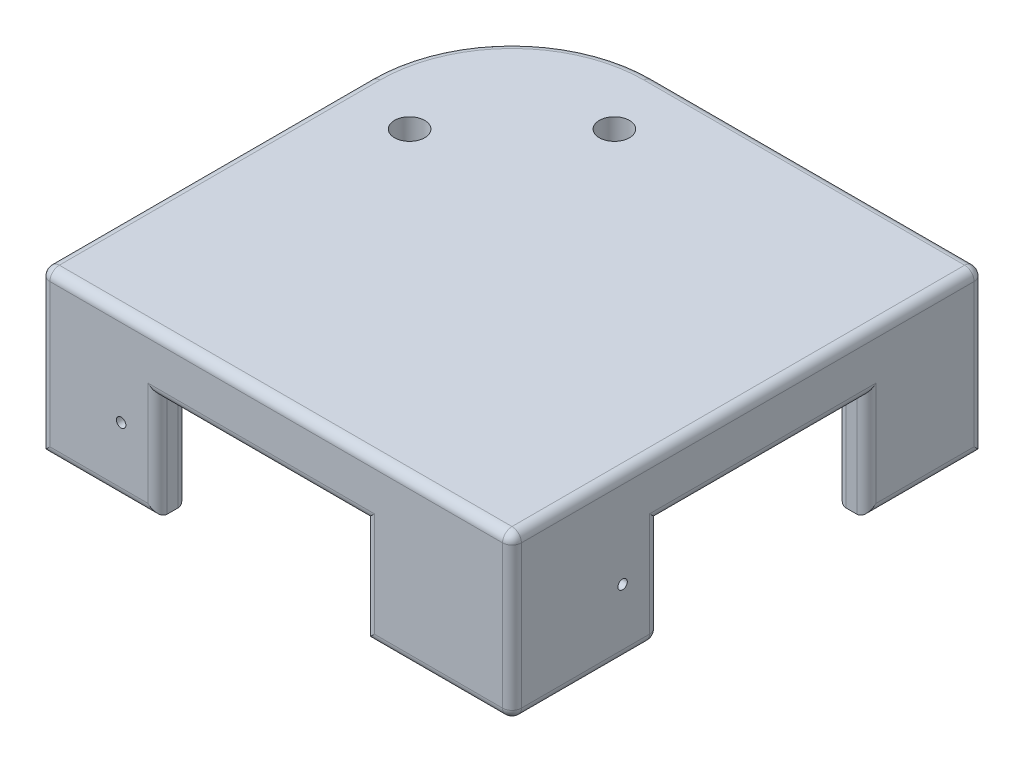
SolidWorks part; units mm, degrees
ref_plane "Front Plane" through (0, 0, 0) normal (0, 0, 1) x (1, 0, 0)
ref_plane "Top Plane" through (0, 0, 0) normal (0, 1, 0) x (1, 0, 0)
ref_plane "Right Plane" through (0, 0, 0) normal (1, 0, 0) x (0, 0, -1)
sketch "Sketch1" plane through (0, 0, 0) normal (0, 1, 0) x (1, 0, 0)
  line L1 (-25, 25) -> (25, 25)
  line L2 (-25, 25) -> (-25, -25)
  line L3 (-25, -25) -> (25, -25)
  line L4 (25, 25) -> (25, -25)
  line L5 (-25, 25) -> (25, -25) construction
  line L6 (-25, -25) -> (25, 25) construction
  point P0 (0, 0)
  dimension "D1" = 50
  dimension "D2" = 50
extrude "Boss-Extrude1" add sketch "Sketch1" along normal blind 3.175
sketch "Sketch2" plane through (0, 0, 0) normal (0, -1, 0) x (-1, 0, 0)
  line L0 (-25, -25) -> (-25, 25) construction
  line L1 (25, -25) -> (-25, -25)
  line L2 (25, -25) -> (25, -21.825)
  line L3 (25, -21.825) -> (-25, -21.825)
  line L4 (-25, -25) -> (-25, -21.825)
  line L5 (25, -25) -> (-25, -21.825) construction
  line L6 (25, -21.825) -> (-25, -25) construction
  line L8 (-25, 25) -> (-21.825, 25)
  line L9 (-25, 25) -> (-25, -21.825)
  line L10 (-25, -21.825) -> (-21.825, -21.825)
  line L11 (-21.825, 25) -> (-21.825, -21.825)
  line L12 (-25, 25) -> (-21.825, -21.825) construction
  line L13 (-25, -21.825) -> (-21.825, 25) construction
  point P4 (0, -23.4125)
  point P11 (-23.4125, 1.5875)
  line M3 (-25, 25) -> (-25, -25)
  line M4 (-25, -25) -> (25, -25)
  line M5 (25, -25) -> (25, 25)
  line M6 (25, 25) -> (-25, 25)
  dimension "D1" = 3.175
  dimension "D2" = 3.175
extrude "Boss-Extrude2" add sketch "Sketch2" along normal blind 14 contours L3 M5 M3 M4 | L11 L3 M6 M3 region at (0, 0, 23.4125) region at (23.4125, 0, -1.5875)
sketch "Sketch3" plane through (0, 0, 21.825) normal (0, 0, -1) x (-1, 0, 0)
  line L0 (25, -7) -> (-21.825, -7) construction
  line L1 (25, -14) -> (25, 0) construction
  line L2 (-21.825, -14) -> (-21.825, 0) construction
  line L3 (-21.825, -7) -> (1.5875, -7) construction
  line L4 (1.5875, -7) -> (1.5875, -14) construction
  line L5 (25, -14) -> (-21.825, -14) construction
  line L6 (16.4475, -7) -> (16.4475, -14) construction
  line L7 (12.5875, -11.05) -> (-9.4125, -11.05)
  line L8 (12.5875, -11.05) -> (12.5875, -2.95)
  line L9 (12.5875, -2.95) -> (-9.4125, -2.95)
  line L10 (-9.4125, -11.05) -> (-9.4125, -2.95)
  line L11 (12.5875, -11.05) -> (-9.4125, -2.95) construction
  line L12 (12.5875, -2.95) -> (-9.4125, -11.05) construction
  line L13 (12.5875, -11.05) -> (-9.4125, -11.05)
  line L14 (12.5875, -11.05) -> (12.5875, -14)
  line L15 (12.5875, -14) -> (-9.4125, -14)
  line L16 (-9.4125, -11.05) -> (-9.4125, -14)
  line L17 (12.5875, -11.05) -> (-9.4125, -14) construction
  line L18 (12.5875, -14) -> (-9.4125, -11.05) construction
  circle A0 centre (16.4475, -7) radius 0.5
  point P16 (1.5875, -12.525)
  line M8 (-21.825, -14) -> (25, -14)
  dimension "D4" = 1
  dimension "D1" = 22
  dimension "D2" = 8.1
  dimension "D3" = 3.86
extrude "Cut-Extrude1" cut sketch "Sketch3" against normal through all contours L10 L7 L8 L9 | L7 L16 L14 M8 | A0 region at (-1.5875, -12.525, 21.825) region at (-1.5875, -7, 21.825) region at (-16.4475, -7, 21.825)
sketch "Sketch4" plane through (21.825, 0, 0) normal (-1, 0, 0) x (0, 0, 1)
  line L0 (21.825, -7) -> (-25, -7) construction
  line L1 (21.825, -14) -> (21.825, 0) construction
  line L2 (-25, -14) -> (-25, 0) construction
  line L3 (-25, -7) -> (-1.5875, -7) construction
  line L4 (-1.5875, -7) -> (-1.5875, -14) construction
  line L5 (-25, -14) -> (21.825, -14) construction
  line L6 (13.2725, -7) -> (13.2725, -14) construction
  line L7 (9.4125, -11.05) -> (-12.5875, -11.05)
  line L8 (9.4125, -11.05) -> (9.4125, -2.95)
  line L9 (9.4125, -2.95) -> (-12.5875, -2.95)
  line L10 (-12.5875, -11.05) -> (-12.5875, -2.95)
  line L11 (9.4125, -11.05) -> (-12.5875, -2.95) construction
  line L12 (9.4125, -2.95) -> (-12.5875, -11.05) construction
  line L13 (9.4125, -11.05) -> (-12.5875, -11.05)
  line L14 (9.4125, -11.05) -> (9.4125, -14)
  line L15 (9.4125, -14) -> (-12.5875, -14)
  line L16 (-12.5875, -11.05) -> (-12.5875, -14)
  line L17 (9.4125, -11.05) -> (-12.5875, -14) construction
  line L18 (9.4125, -14) -> (-12.5875, -11.05) construction
  circle A0 centre (13.2725, -7) radius 0.5
  point P16 (-1.5875, -12.525)
  line M8 (-25, -14) -> (21.825, -14)
  dimension "D4" = 1
  dimension "D1" = 8.1
  dimension "D2" = 22
  dimension "D3" = 3.86
extrude "Cut-Extrude2" cut sketch "Sketch4" against normal through all contours L10 L7 L8 L9 | L7 L16 L14 M8 | A0 region at (21.825, -12.525, -1.5875) region at (21.825, -7, -1.5875) region at (21.825, -7, 13.2725)
sketch "Sketch5" plane through (0, 3.175, 0) normal (0, 1, 0) x (1, 0, 0)
  line L0 (-25, 0) -> (0, 25) construction
  line L1 (-25, 25) -> (0, 25) construction
  line L2 (-25, 25) -> (-25, 0) construction
  line L3 (-25, 0) -> (0, 0) construction
  line L4 (0, 25) -> (0, 0) construction
  line L5 (-25, 25) -> (0, 0) construction
  line L6 (-25, 0) -> (0, 25) construction
  circle A0 centre (-7.0711, 17.9289) radius 1.6
  circle A1 centre (-17.9289, 7.0711) radius 1.6
  point P4 (-12.5, 12.5)
  dimension "D4" = 3.2
  dimension "D1" = 25
  dimension "D2" = 25
  dimension "D3" = 10
extrude "Cut-Extrude3" cut sketch "Sketch5" against normal through all
fillet "Fillet1" radius 1 34 edges at (25, -14, -18.7938) (25, -8.475, -12.5875) (21.825, -14, -18.7938) (21.825, -8.475, -12.5875) (25, -8.475, 9.4125) (25, -2.95, -1.5875) (21.825, -2.95, -1.5875) (25, -14, 17.2062) (17.2062, -14, 25) (21.825, -8.475, 9.4125) (23.4125, -14, 9.4125) (21.825, -14, 15.6187) (15.6187, -14, 21.825) (9.4125, -8.475, 21.825) (9.4125, -8.475, 25) (-1.5875, -2.95, 25) (-1.5875, -2.95, 21.825) (-12.5875, -8.475, 25) (-12.5875, -8.475, 21.825) (-18.7937, -14, 25) (-18.7937, -14, 21.825) (-25, -5.4125, 25) (25, -5.4125, 25) (25, -5.4125, -25) (25, 3.175, 0) (0, 3.175, 25) (-25, 3.175, 0) (0, 3.175, -25)
fillet "Fillet2" radius 15 3 edges at (-24.7071, 0.2929, -24.7071) (-24.7071, 2.8821, -24.7071) (-25, 1.5875, -25)
